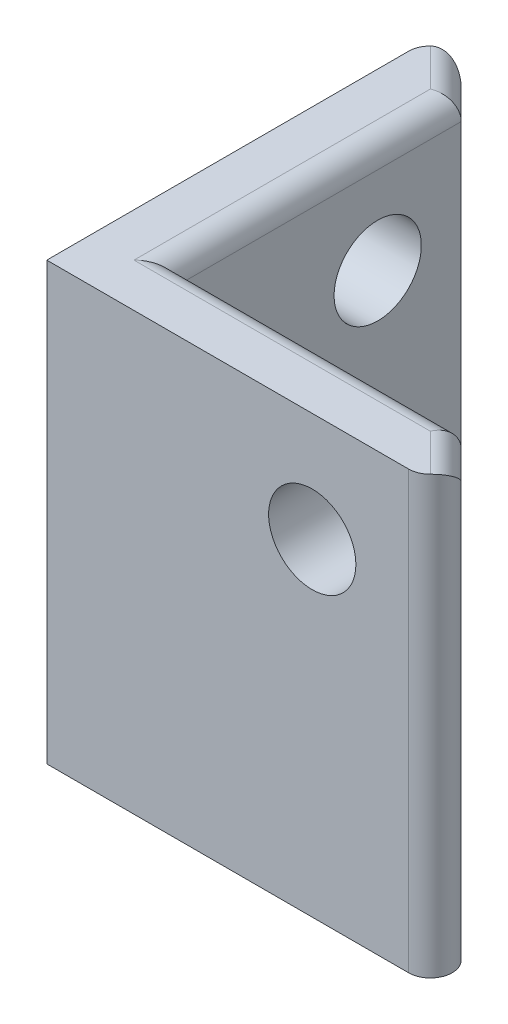
SolidWorks part; units mm, degrees
ref_plane "前视" through (0, 0, 0) normal (0, 0, 1) x (1, 0, 0)
ref_plane "上视" through (0, 0, 0) normal (0, 1, 0) x (1, 0, 0)
ref_plane "右视" through (0, 0, 0) normal (1, 0, 0) x (0, 0, -1)
sketch "Sketch1" plane through (0, 0, 0) normal (0, 1, 0) x (1, 0, 0)
  line L0 (0, 0) -> (0, 19)
  line L1 (0, 0) -> (19, 0)
  line L2 (19, 0) -> (0, 19)
  dimension "D1" = 19
  dimension "D2" = 19
extrude "Boss-Extrude1" add sketch "Sketch1" along normal blind 5
sketch "Sketch2" plane through (0, 5, 0) normal (0, 1, 0) x (1, 0, 0)
  line L0 (0, 19) -> (0, 0)
  line L1 (0, 0) -> (19, 0)
  line L2 (19, 0) -> (16, 3)
  line L3 (19, 0) -> (0, 19) construction
  line L4 (16, 3) -> (3, 3)
  line L5 (3, 3) -> (3, 16)
  line L6 (3, 16) -> (0, 19)
  dimension "D1" = 3
  dimension "D2" = 3
extrude "Boss-Extrude2" add sketch "Sketch2" along normal blind 15
sketch "Sketch3" plane through (0, 0, 0) normal (0, 0, 1) x (1, 0, 0)
  line L0 (0, 20) -> (0, 0) construction
  line L1 (0, 0) -> (19, 0) construction
  circle A0 centre (12.17, 15) radius 2
  dimension "D1" = 12.17
  dimension "D2" = 15
extrude "Cut-Extrude1" cut sketch "Sketch3" against normal through all
sketch "Sketch4" plane through (0, 0, 0) normal (-1, 0, 0) x (0, 0, 1)
  line L0 (-19, 0) -> (0, 0) construction
  line L1 (0, 20) -> (0, 0) construction
  circle A0 centre (-12.17, 15) radius 2
  dimension "D1" = 15
  dimension "D2" = 12.17
extrude "Cut-Extrude2" cut sketch "Sketch4" against normal through all
fillet "Fillet1" radius 1 6 edges at (9.5, 20, -3) (3, 20, -9.5) (1.5, 20, -17.5) (17.5, 20, -1.5) (19, 10, 0) (0, 10, -19)
sketch "Sketch5" plane through (0, 5, 0) normal (0, 1, 0) x (1, 0, 0)
  line L0 (16, 3) -> (3, 3) construction
  line L1 (3, 3) -> (3, 16) construction
  circle A0 centre (7, 7) radius 1.75
  dimension "D1" = 4
  dimension "D2" = 4
extrude "Cut-Extrude3" cut sketch "Sketch5" against normal through all
